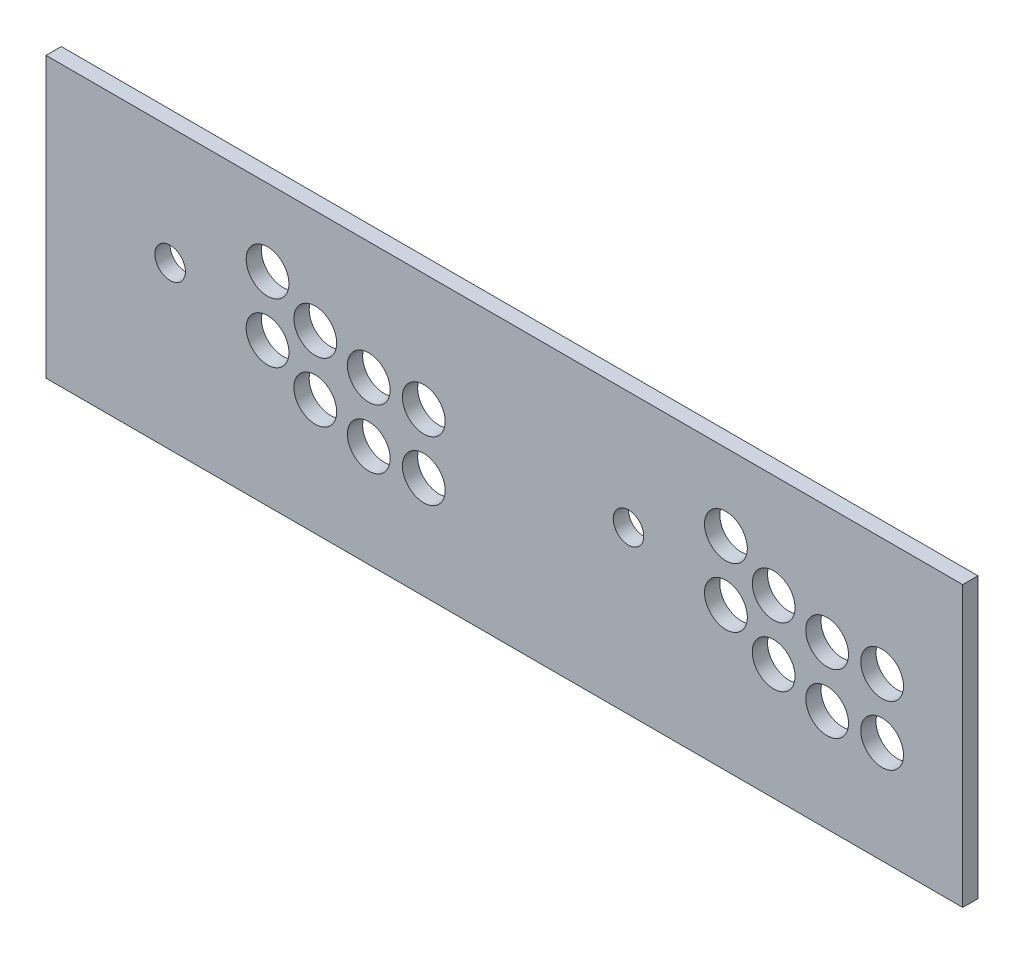
SolidWorks part; units mm, degrees
ref_plane "Plan de face" through (0, 0, 0) normal (0, 0, 1) x (1, 0, 0)
ref_plane "Plan de dessus" through (0, 0, 0) normal (0, 1, 0) x (1, 0, 0)
ref_plane "Plan de droite" through (0, 0, 0) normal (1, 0, 0) x (0, 0, -1)
sketch "Esquisse1" plane through (0, 0, 0) normal (0, 0, 1) x (1, 0, 0)
  line L1 (0, 0) -> (600, 0)
  line L2 (0, 0) -> (0, 183)
  line L3 (0, 183) -> (600, 183)
  line L4 (600, 0) -> (600, 183)
  dimension "D1" = 183
  dimension "D2" = 600
extrude "Boss.-Extru.1" add sketch "Esquisse1" along normal blind 10
sketch "Esquisse3" plane through (0, 0, 0) normal (0, 0, -1) x (-1, 0, 0)
  line L13 (-300, 183) -> (-300, 0) construction
  line L14 (-600, 183) -> (0, 183) construction
  line L15 (0, 0) -> (-600, 0) construction
  circle A1 centre (-247.25, 67) radius 14
  circle A2 centre (-211.25, 67) radius 14
  circle A3 centre (-81.25, 106) radius 10
  circle A4 centre (-176.25, 76) radius 14
  circle A5 centre (-145, 94) radius 14
  circle A6 centre (-247.25, 106) radius 14
  circle A7 centre (-211.25, 106) radius 14
  circle A8 centre (-176.25, 115) radius 14
  circle A9 centre (-145, 133) radius 14
  dimension "D12" = 28
  dimension "D13" = 20
extrude "Enlèv. mat.-Extru.1" cut sketch "Esquisse3" against normal blind 10
pattern_linear "Répétition linéaire1" count 2 spacing 300 along (1, 0, 0) of "Enlèv. mat.-Extru.1"
